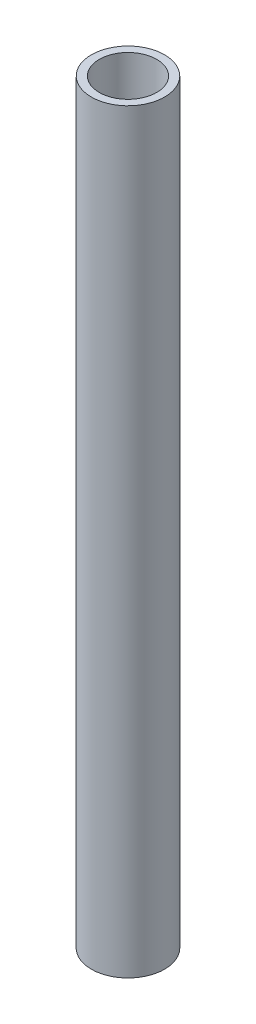
SolidWorks part; units mm, degrees
ref_plane "Alzado" through (0, 0, 0) normal (0, 0, 1) x (1, 0, 0)
ref_plane "Planta" through (0, 0, 0) normal (0, 1, 0) x (1, 0, 0)
ref_plane "Vista lateral" through (0, 0, 0) normal (1, 0, 0) x (0, 0, -1)
sketch "Croquis2" plane through (0, 0, 0) normal (0, 1, 0) x (1, 0, 0)
  circle A0 centre (0, 0) radius 16
extrude "Saliente-Extruir1" add sketch "Croquis2" along normal blind 165 and the other way blind 165
sketch "Croquis4" plane through (0, 0, 0) normal (0, 1, 0) x (1, 0, 0)
  circle A0 centre (0, 0) radius 12.5508
extrude "Cortar-Extruir1" cut sketch "Croquis4" along normal mid plane 421
